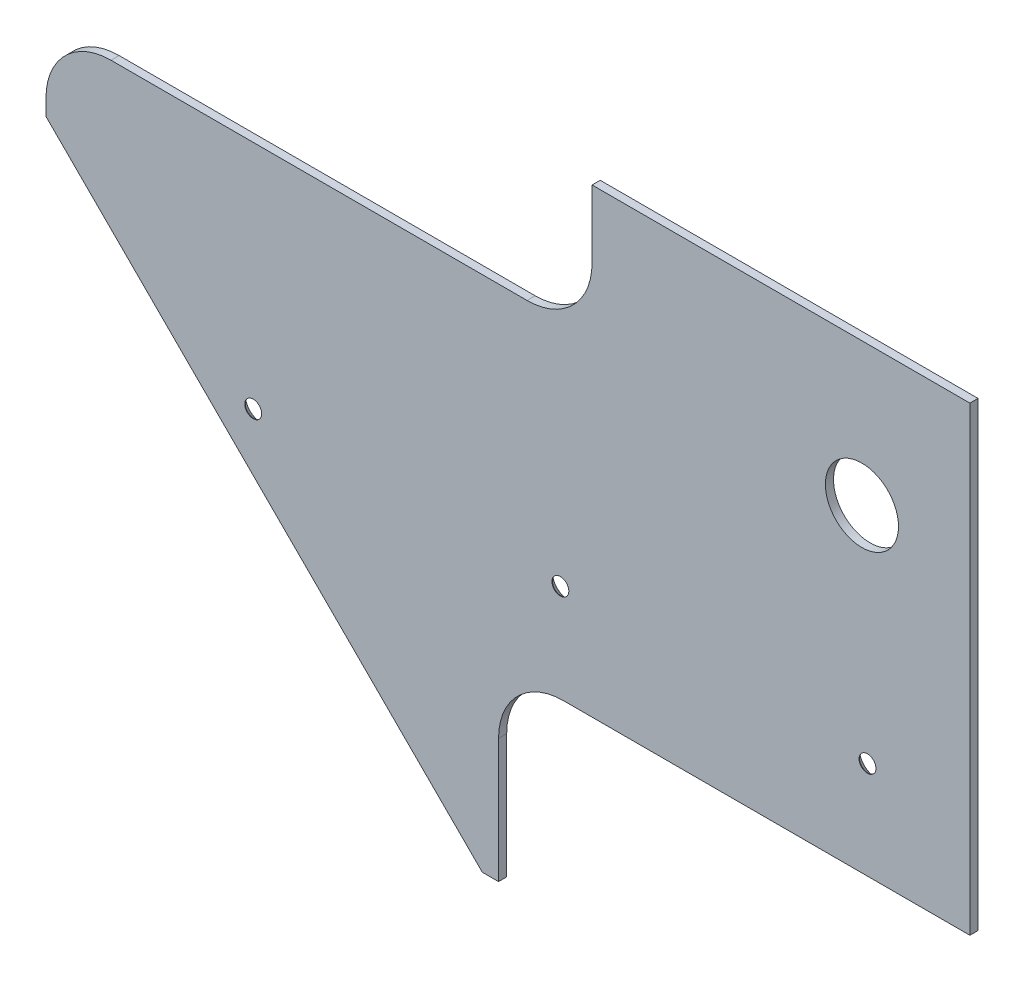
SolidWorks part; units mm, degrees
ref_plane "Front Plane" through (0, 0, 0) normal (0, 0, 1) x (1, 0, 0)
ref_plane "Top Plane" through (0, 0, 0) normal (0, 1, 0) x (1, 0, 0)
ref_plane "Right Plane" through (0, 0, 0) normal (1, 0, 0) x (0, 0, -1)
sketch "Sketch1" plane through (0, 0, 0) normal (0, 0, 1) x (1, 0, 0)
  line L0 (-138.2594, 48.9915) -> (32.2106, -121.4785)
  line L1 (32.2106, -121.4785) -> (222.7106, -121.4785)
  line L2 (-138.2594, 145.2215) -> (-138.2594, 48.9915)
  line L3 (-138.2594, 145.2215) -> (222.7106, 145.2215)
  line L4 (222.7106, -121.4785) -> (222.7106, 145.2215)
  circle A0 centre (180.538, 76.832) radius 14.2875
  circle A2 centre (180.538, 76.832) radius 64.9605 construction
  circle A3 centre (180.538, 76.832) radius 318.7974 construction
  point P0 (0, 0)
  point P2 (180.538, 76.832)
  dimension "D4" = 198.3105
  dimension "D1" = 45
  dimension "D2" = 266.7
  dimension "D5" = 245.11
extrude "Boss-Extrude1" add sketch "Sketch1" along normal blind 3.175
sketch "Sketch2" plane through (0, 0, 3.175) normal (0, 0, 1) x (1, 0, 0)
  line L0 (32.2106, -121.4785) -> (222.7106, -121.4785) construction
  line L1 (222.7634, -121.4785) -> (38.5606, -121.4785)
  line L2 (222.7634, -121.4785) -> (222.7634, -47.5645)
  line L3 (222.7634, -47.5645) -> (38.5606, -47.5645)
  line L4 (38.5606, -121.4785) -> (38.5606, -47.5645)
extrude "Cut-Extrude1" cut sketch "Sketch2" against normal through all contours L3 L4 L1 L2
fillet "Fillet1" radius 25.4 1 edges at (38.5606, -47.5645, 1.5875)
sketch "Sketch4" plane through (0, 0, 3.175) normal (0, 0, 1) x (1, 0, 0)
  line L1 (-138.2594, 145.2215) -> (-138.2594, 48.9915) construction
  line L3 (-138.2594, 145.2215) -> (75.1006, 145.2215)
  line L4 (-138.2594, 145.2215) -> (-138.2594, 80.7415)
  line L5 (-138.2594, 80.7415) -> (75.1006, 80.7415)
  line L6 (75.1006, 145.2215) -> (75.1006, 80.7415)
extrude "Cut-Extrude2" cut sketch "Sketch4" against normal through all contours L5 L6 L3 L4
fillet "Fillet2" radius 25.4 2 edges at (-138.2594, 80.7415, 1.5875) (75.1006, 80.7415, 1.5875)
sketch "Sketch7" plane through (0, 0, 3.175) normal (0, 0, 1) x (1, 0, 0)
  line L0 (222.7106, -47.5645) -> (222.7106, 145.2215) construction
  line L1 (75.1006, 145.2215) -> (222.7106, 145.2215)
  line L2 (75.1006, 145.2215) -> (75.1006, 132.5215)
  line L3 (75.1006, 132.5215) -> (222.7106, 132.5215)
  line L4 (222.7106, 145.2215) -> (222.7106, 132.5215)
  dimension "D1" = 12.7
extrude "Cut-Extrude4" cut sketch "Sketch7" against normal through all
hole_wizard "CSK for M6 Flat Head Machine Screw1" positions "Sketch9" profile "Sketch8" countersink size "M6" standard "ANSI Metric" end condition through all
sketch "Sketch9" plane through (0, 0, 0) normal (0, 0, -1) x (-1, 0, 0)
  line L1 (-222.7106, -47.5645) -> (-63.9606, -47.5645) construction
  line L5 (-222.7106, -47.5645) -> (-222.7106, 132.5215) construction
  point P0 (-182.7106, -9.4645)
  point P3 (-62.7106, -9.4645)
  point P6 (57.2894, -9.4645)
  dimension "D1" = 38.1
  dimension "D2" = 38.1
  dimension "D3" = 120
  dimension "D4" = 120
  dimension "D5" = 40
  dimension "D6" = 38.1
sketch "Sketch8" plane through (182.7106, -9.4645, 0) normal (1, 0, 0) x (0, 1, 0)
  line L0 (0, 0) -> (0, 3.175)
  line L1 (0, 3.175) -> (3.3, 3.175)
  line L2 (3.3, 3.175) -> (3.3, 3)
  line L3 (3.3, 3) -> (6.3, 0)
  line L5 (6.3, 0) -> (0, 0)
  line L6 (-3.3, 3) -> (-6.3, 0) construction
  line L11 (0, -6.35) -> (0, 107.95) construction
  dimension "Thru Hole Dia." = 6.6
  dimension "Thru Hole Depth" = 3.175
  dimension "Near C'Sink Dia." = 12.6
  dimension "Near C'Sink Angle" = 90
